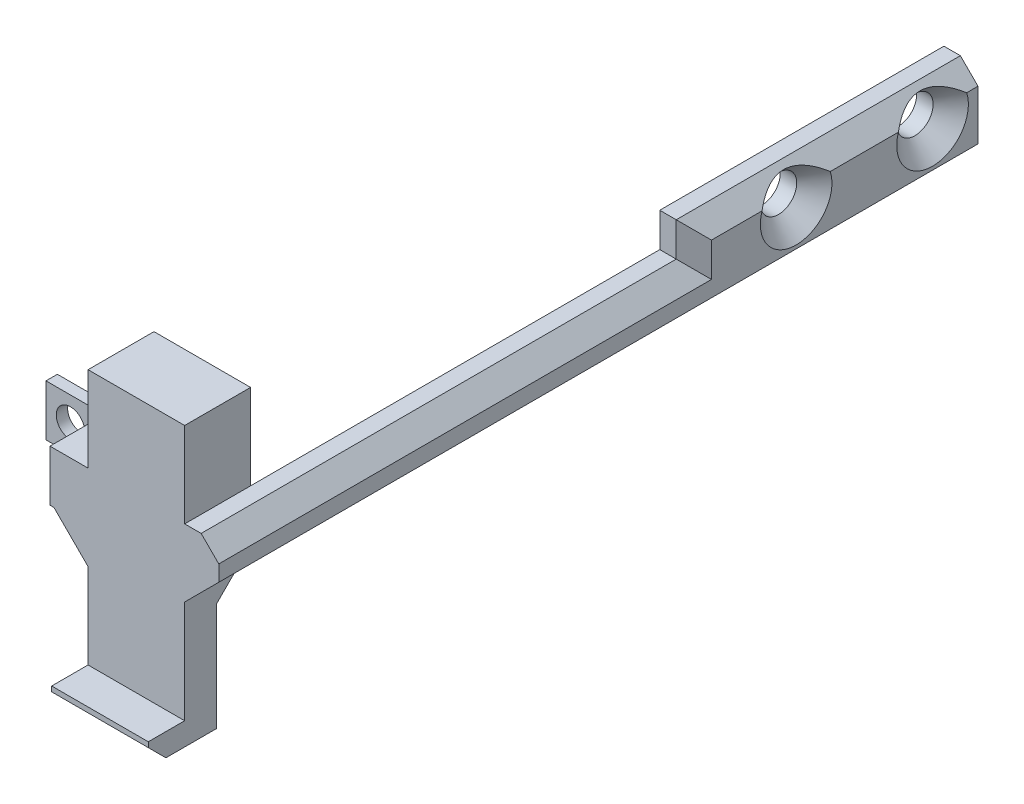
SolidWorks part; units mm, degrees
ref_plane "Front Plane" through (0, 0, 0) normal (0, 0, 1) x (1, 0, 0)
ref_plane "Top Plane" through (0, 0, 0) normal (0, 1, 0) x (1, 0, 0)
ref_plane "Right Plane" through (0, 0, 0) normal (1, 0, 0) x (0, 0, -1)
sketch "Sketch1" plane through (0, 0, 0) normal (0, 0, 1) x (1, 0, 0)
  line L0 (0, 0) -> (0, 4.5)
  line L1 (0, 4.5) -> (8.5, 4.5)
  line L2 (8.5, 4.5) -> (8.5, 12)
  line L3 (8.5, 12) -> (17, 12)
  line L4 (17, 12) -> (17, 0)
  line L5 (8.5, 0) -> (0, 0)
  line L8 (8.5, 0) -> (8.5, -12.5)
  line L9 (8.5, -12.5) -> (17, -12.5)
  line L10 (17, 0) -> (17, -12.5)
  circle A0 centre (2.15, 2.35) radius 1.25
  dimension "D2" = 2.5
  dimension "D1" = 4.5
  dimension "D3" = 8.5
  dimension "D4" = 2.15
  dimension "D5" = 2.15
  dimension "D6" = 17
  dimension "D7" = 12
  dimension "D9" = 12.5
extrude "Boss-Extrude1" add sketch "Sketch1" along normal blind 1
sketch "Sketch2" plane through (0, 0, 1) normal (0, 0, 1) x (1, 0, 0)
  line L0 (5.15, 4.5) -> (5.15, 0)
  line L6 (0, 0) -> (8.5, 0)
  line L7 (17, -12.5) -> (17, 12)
  line L8 (17, 12) -> (8.5, 12)
  line L9 (8.5, 12) -> (8.5, 4.5)
  line L10 (8.5, 4.5) -> (0, 4.5)
  line L11 (0, 4.5) -> (0, 0)
  line L12 (5.15, 0) -> (8.5, 0)
  line L13 (17, -12.5) -> (17, 12)
  line L14 (17, 12) -> (8.5, 12)
  line L15 (8.5, 12) -> (8.5, 4.5)
  line L16 (8.5, 4.5) -> (5.15, 4.5)
  line L21 (8.5, 0) -> (8.5, -12.5)
  line L22 (8.5, 0) -> (8.5, -12.5)
  line L23 (8.5, -12.5) -> (17, -12.5)
  line L24 (8.5, -12.5) -> (17, -12.5)
  circle A0 centre (2.15, 2.35) radius 1.25 construction
  dimension "D2" = 3
  dimension "D1" = 0
extrude "Boss-Extrude2" add sketch "Sketch2" along normal blind 8
sketch "Sketch3" plane through (0, 0, 9) normal (0, 0, 1) x (1, 0, 0)
  line L0 (8.5, 12) -> (8.5, 4.5) construction
  line L1 (8.5, 10) -> (17, 10)
  line L2 (8.5, 10) -> (8.5, 4.5)
  line L3 (8.5, -10.5) -> (17, -10.5)
  line L4 (17, 10) -> (17, -10.5)
  line L5 (17, -12.5) -> (17, 12) construction
  line L6 (17, 12) -> (8.5, 12) construction
  line L9 (5.15, 4.5) -> (8.5, 4.5)
  line L10 (5.15, 4.5) -> (5.15, -10.5)
  line L11 (5.15, -10.5) -> (8.5, -10.5)
  dimension "D1" = 2
  dimension "D2" = 20.5
extrude "Cut-Extrude1" cut sketch "Sketch3" against normal blind 3.2
sketch "Sketch4" plane through (17, 0, 0) normal (1, 0, 0) x (0, 0, -1)
  line L0 (51, 7.5) -> (51, 0) construction
  line L1 (-5.8, 0) -> (61, 0)
  line L2 (-5.8, 0) -> (-5.8, 4.5)
  line L3 (-5.8, 4.5) -> (36, 4.5)
  line L4 (61, 0) -> (61, 4.5)
  line L7 (61, 4.5) -> (61, 7.5)
  line L8 (61, 7.5) -> (36, 7.5)
  line L9 (36, 4.5) -> (36, 7.5)
  line L10 (-5.8, -10.5) -> (-5.8, 10) construction
  circle A0 centre (57, 5) radius 1.6
  circle A1 centre (45, 5) radius 1.6
  dimension "D4" = 3.2
  dimension "D5" = 3.2
  dimension "D1" = 4.5
  dimension "D2" = 66.8
  dimension "D3" = 56.8
  dimension "D6" = 6
  dimension "D7" = 6
  dimension "D8" = 5
  dimension "D9" = 5
  dimension "D10" = 15
  dimension "D11" = 3
extrude "Boss-Extrude3" add sketch "Sketch4" along normal blind 3
chamfer "Chamfer1" distance 1.55 angle 45 2 edges at (20, 6.6, -57) (20, 6.6, -45)
chamfer "Chamfer2" distance 1.55 angle 45 4 edges at (20, 7.5, -39.5418) (20, 6, -36) (20, 4.5, -15.1) (12.75, 12, 9)
chamfer "Chamfer3" distance 1.55 angle 45 2 edges at (20, 0, -27.6) (12.75, -12.5, 9)
sketch "Sketch5" plane through (0, 0, 0) normal (0, 0, -1) x (-1, 0, 0)
  line L1 (-17, -12.5) -> (-8.5, -12.5)
  line L2 (-17, -12.5) -> (-17, 0)
  line L3 (-17, 0) -> (-8.5, 0)
  line L4 (-8.5, -12.5) -> (-8.5, 0)
extrude "Cut-Extrude2" cut sketch "Sketch5" against normal blind 3
chamfer "Chamfer4" distance 3 angle 45 2 edges at (8.5, 0, 4.4) (12.75, 0, 3)
chamfer "Chamfer5" distance 1.45 angle 45 1 edges at (17, 0, 2.9)
sketch "Sketch6" plane through (0, 10, 0) normal (0, -1, 0) x (1, 0, 0)
  line L4 (17, 9) -> (8.5, 9)
  line L5 (8.5, 9) -> (8.5, 5.8)
  line L6 (8.5, 5.8) -> (17, 5.8)
  line L7 (17, 5.8) -> (17, 9)
  line L8 (17, 9) -> (8.5, 9)
  line L9 (8.5, 9) -> (8.5, 5.8)
  line L10 (8.5, 5.8) -> (17, 5.8)
  line L11 (17, 5.8) -> (17, 9)
  dimension "D1" = 0
extrude "Cut-Extrude3" cut sketch "Sketch6" against normal through all
